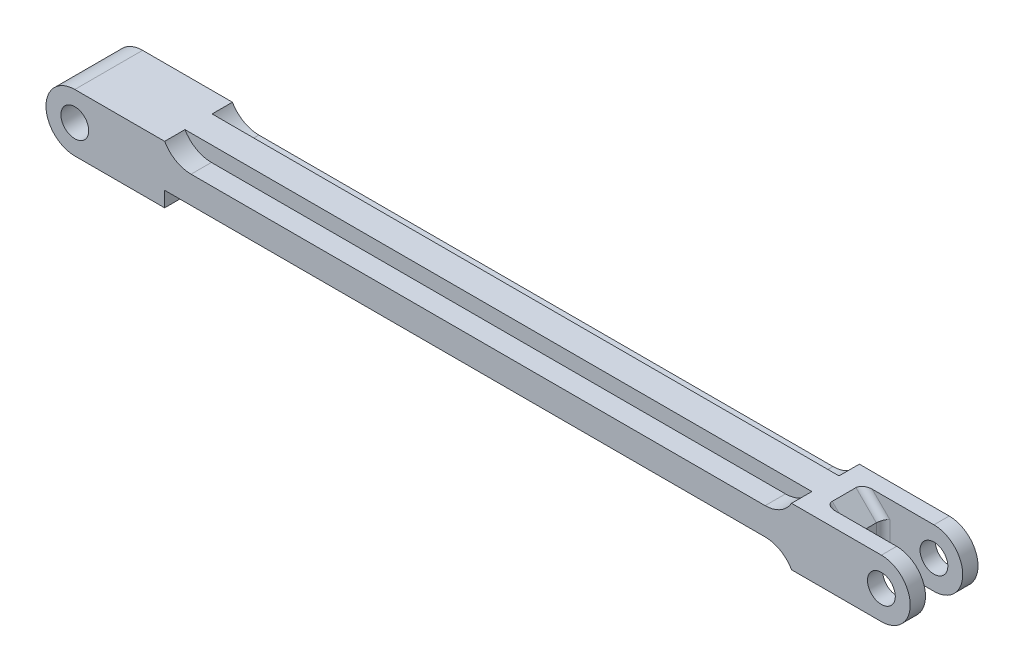
SolidWorks part; units mm, degrees
ref_plane "Front Plane" through (0, 0, 0) normal (0, 0, 1) x (1, 0, 0)
ref_plane "Top Plane" through (0, 0, 0) normal (0, 1, 0) x (1, 0, 0)
ref_plane "Right Plane" through (0, 0, 0) normal (1, 0, 0) x (0, 0, -1)
sketch "Sketch1" plane through (0, 0, 0) normal (0, 0, 1) x (1, 0, 0)
  line L0 (0, 0) -> (237.95, 0) construction
  line L1 (0, 8.5) -> (237.95, 8.5)
  line L2 (0, -8.5) -> (237.95, -8.5)
  line L3 (118.975, -8.5) -> (118.975, 8.5) construction
  arc A0 (0, 8.5) -> (0, -8.5) centre (0, 0) ccw
  arc A1 (237.95, -8.5) -> (237.95, 8.5) centre (237.95, 0) ccw
  circle A2 centre (0, 0) radius 4.1
  circle A3 centre (237.95, 0) radius 4.1
  point P3 (118.975, 0)
  dimension "D2" = 8.5
  dimension "D3" = 8.2
  dimension "D1" = 237.95
extrude "Corpo" add sketch "Sketch1" along normal mid plane 20
sketch "Sketch2" plane through (0, 8.5, 0) normal (0, 1, 0) x (1, 0, 0)
  line L0 (246.45, 0) -> (222.95, 0) construction
  line L1 (246.45, -10) -> (246.45, 10) construction
  line L3 (246.45, -5.5) -> (222.95, -5.5)
  line L4 (246.45, -5.5) -> (246.45, 5.5)
  line L5 (246.45, 5.5) -> (222.95, 5.5)
  line L6 (222.95, -5.5) -> (222.95, 5.5)
  line L7 (246.45, -5.5) -> (222.95, 5.5) construction
  line L8 (246.45, 5.5) -> (222.95, -5.5) construction
  point P5 (234.7, 0)
  point P10 (214.7141, 0)
  dimension "D1" = 23.5
  dimension "D2" = 11
extrude "Encaixe do Pino Tirante" cut sketch "Sketch2" against normal through all
sketch "Sketch3" plane through (0, 8.5, 0) normal (0, 1, 0) x (1, 0, 0)
  line L0 (211.45, -10) -> (211.45, 10) construction
  line L1 (-8.5, 10) -> (-8.5, -10) construction
  line L2 (237.95, 10) -> (0, 10) construction
  line L3 (26.5, -10) -> (26.5, 10) construction
  line L6 (222.95, 5.5) -> (222.95, -5.5) construction
  line L7 (26.5, 0) -> (222.95, 0) construction
  line L8 (26.5, -4) -> (211.45, -4)
  line L9 (26.5, 10) -> (211.45, 10)
  line L10 (26.5, 10) -> (26.5, 4)
  line L11 (26.5, 4) -> (211.45, 4)
  line L12 (211.45, 10) -> (211.45, 4)
  line L13 (211.45, -10) -> (211.45, -4)
  line L14 (26.5, -10) -> (211.45, -10)
  line L15 (26.5, -10) -> (26.5, -4)
  line L16 (246.45, -10) -> (246.45, -5.5) construction
  point P3 (222.95, 0)
  dimension "D1" = 35
  dimension "D2" = 6
  dimension "D3" = 35
extrude "Corte Superior" cut sketch "Sketch3" against normal blind 4.5
mirror "Corte Inferior" about plane through (0, 0, 0) normal (0, 1, 0) of "Corte Superior"
fillet "Raios de 9mm" radius 9 6 edges at (26.5, 4, 7) (26.5, 4, -7) (211.45, 4, -7) (211.45, -4, -7) (211.45, -4, 7) (211.45, 4, 7)
chamfer "Chanfros 6x45°" distance 6 angle 45 2 edges at (222.95, -8.5, 0) (222.95, 8.5, 0)
fillet "Raios 2mm" radius 2 6 edges at (219.95, 5.5, 5.5) (219.95, -5.5, 5.5) (219.95, -5.5, -5.5) (219.95, 5.5, -5.5) (222.95, 0, 5.5) (222.95, 0, -5.5)
